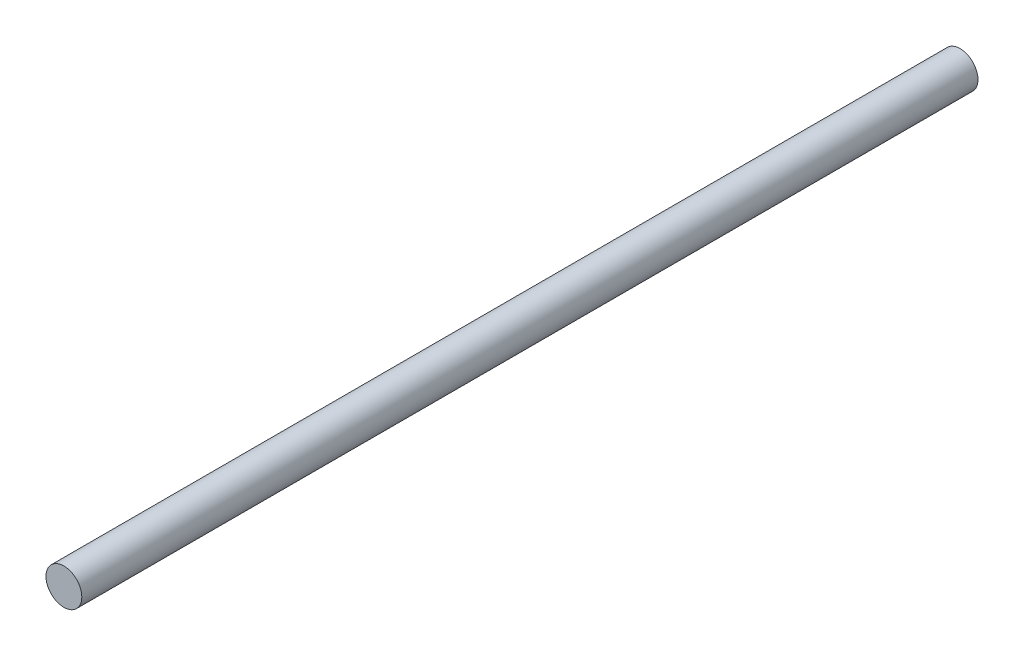
SolidWorks part; units mm, degrees
material "1060 Alloy"
ref_plane "Front Plane" through (0, 0, 0) normal (0, 0, 1) x (1, 0, 0)
ref_plane "Top Plane" through (0, 0, 0) normal (0, 1, 0) x (1, 0, 0)
ref_plane "Right Plane" through (0, 0, 0) normal (1, 0, 0) x (0, 0, -1)
sketch "Sketch2" plane through (0, 0, 0) normal (0, 0, 1) x (1, 0, 0)
  circle A0 centre (0, 0) radius 6
  dimension "D1" = 12
extrude "Boss-Extrude1" add sketch "Sketch2" along normal blind 300
